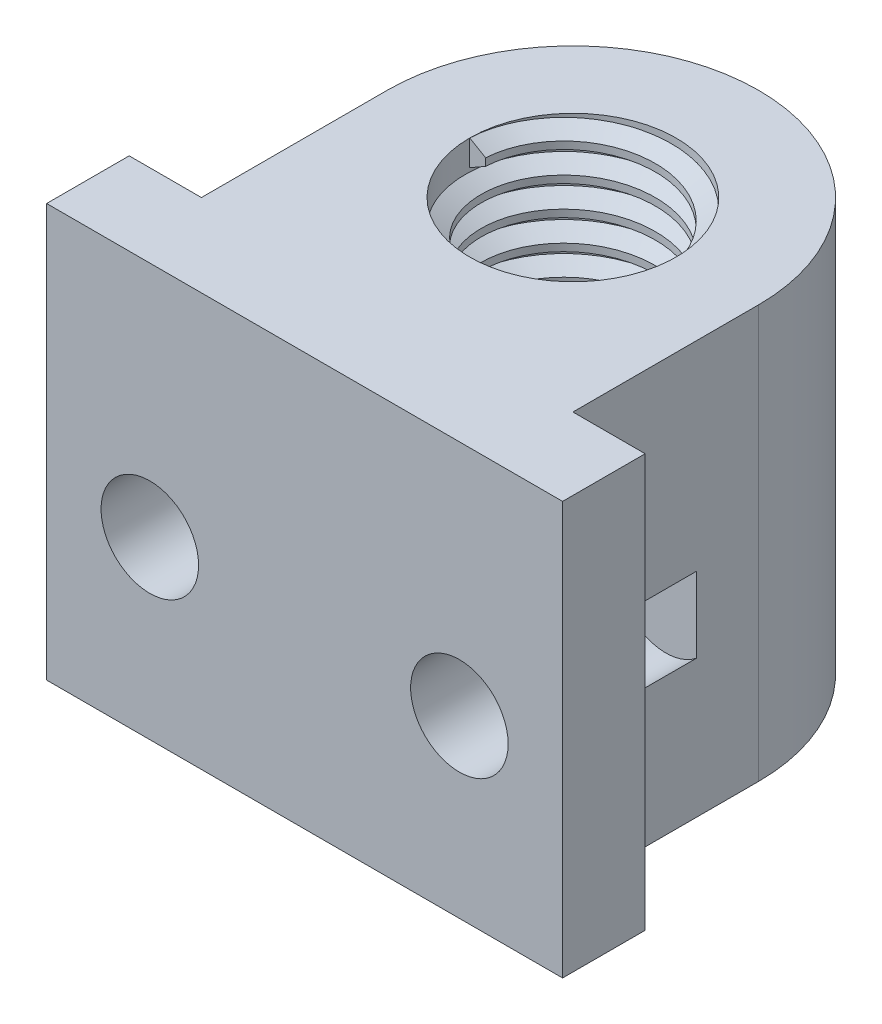
SolidWorks part; units mm, degrees
other "Markup1"
sketch "Sketch2"
ref_plane "Front Plane" through (0, 0, 0) normal (0, 0, 1) x (1, 0, 0)
ref_plane "Top Plane" through (0, 0, 0) normal (0, 1, 0) x (1, 0, 0)
ref_plane "Right Plane" through (0, 0, 0) normal (1, 0, 0) x (0, 0, -1)
sketch "Sketch1" plane through (0, 0, 0) normal (0, 1, 0) x (1, 0, 0)
  line L0 (-7.9375, -5.715) -> (7.9375, -5.715)
  line L1 (0, -5.715) -> (0, 0) construction
  line L2 (-7.9375, -5.715) -> (-7.9375, -8.255)
  line L3 (-7.9375, -8.255) -> (7.9375, -8.255)
  line L4 (7.9375, -8.255) -> (7.9375, -5.715)
  line L5 (-5.715, 0) -> (-5.715, -5.715)
  line L6 (5.715, 0) -> (5.715, -5.715)
  line L7 (-4.7625, -6.985) -> (4.7625, -6.985) construction
  line L8 (0, -6.985) -> (0, -5.715) construction
  circle A0 centre (0, 0) radius 3.175
  circle A1 centre (0, 0) radius 5.715
  point P7 (-4.7625, -6.985)
  point P8 (4.7625, -6.985)
  point P15 (0, 0)
  point P16 (-7.9375, -6.985)
  point P18 (-4.7625, -6.985)
  point P19 (-7.5349, -8.255)
  point P20 (-6.9407, -8.255)
  dimension "D1" = 6.35
  dimension "D2" = 2.54
  dimension "D3" = 2.54
  dimension "D4" = 9.525
  dimension "D5" = 3.175
extrude "Boss-Extrude1" add sketch "Sketch1" along normal blind 12.7 contours A1 A0 | A1 L5 L0 | A1 L0 L6 | L3 L4 L0 L2 region at (0, 0, 6.985) region at (-4.4385, 0, 4.4385) region at (4.4385, 0, 4.4385) region at (-3.9268, 0, 3.9268)
thread "Thread1" pitch 0.9071 method extrude trim with end face yes profile "Thread Profile1" start angle 0, offset 0, length 0, pitch 0.9071, diameter 6.35
ref_plane "Plane1" through (-3.175, 12.7, 0) normal (0, 0, 1) x (-1, 0, 0)
sketch "Thread Profile1" plane through (-3.175, 12.7, 0) normal (0, 0, 1) x (-1, 0, 0)
  line L0 (0, 0) -> (0, 0.9071) construction
  line L11 (0, 0) -> (0, 0.7937)
  line L12 (0, 0.7937) -> (-0.491, 0.5103)
  line L13 (-0.491, 0.5103) -> (-0.491, 0.2835)
  line L15 (-0.491, 0.2835) -> (0, 0)
  line L17 (-0.491, 0.3969) -> (0, 0.3969) construction
  point P2 (0, 0)
  dimension "Pitch" = 0.9071
  dimension "Profile_Angle" = 60
  dimension "Profile_Land" = 0.2268
  dimension "Profile_Height" = 0.491
sketch "Sketch3" plane through (0, 0, 8.255) normal (0, 0, 1) x (1, 0, 0)
  line L0 (-4.7625, 5.3975) -> (4.7625, 5.3975) construction
  line L1 (0, 5.3975) -> (0, 0) construction
  line L2 (-7.9375, 12.7) -> (7.9375, 12.7) construction
  circle A0 centre (-4.7625, 5.3975) radius 1.5
  circle A1 centre (4.7625, 5.3975) radius 1.5
  point P7 (-3.495, 7.6463)
  dimension "D1" = 3
  dimension "D2" = 9.525
  dimension "D3" = 7.3025
extrude "Cut-Extrude1" cut sketch "Sketch3" against normal blind 6.35
